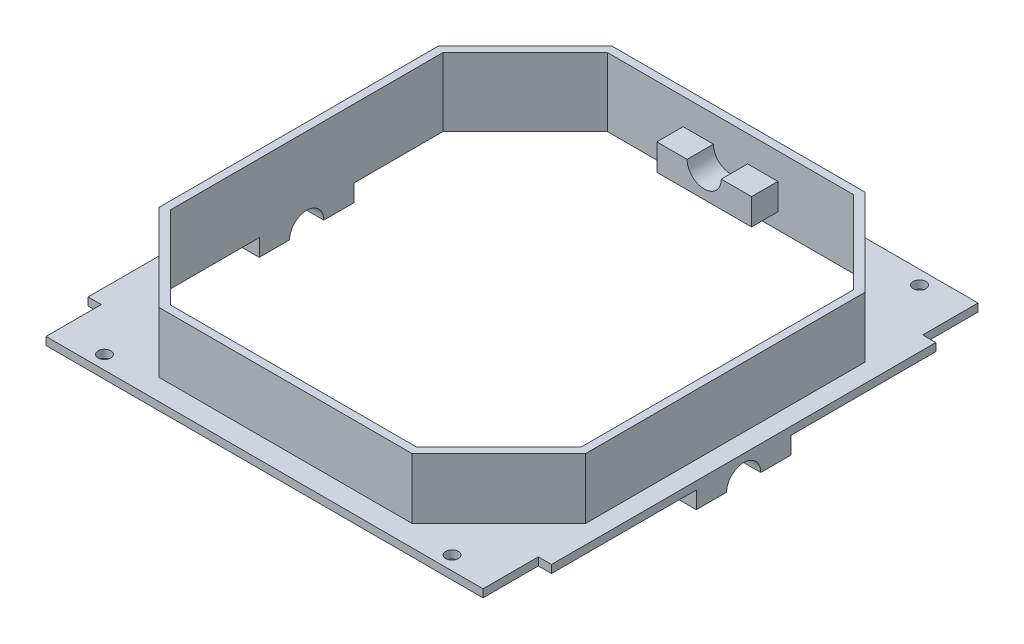
SolidWorks part; units mm, degrees
ref_plane "Front Plane" through (0, 0, 0) normal (0, 0, 1) x (1, 0, 0)
ref_plane "Top Plane" through (0, 0, 0) normal (0, 1, 0) x (1, 0, 0)
ref_plane "Right Plane" through (0, 0, 0) normal (1, 0, 0) x (0, 0, -1)
sketch "Sketch1" plane through (0, 0, 0) normal (0, 1, 0) x (1, 0, 0)
  line L5 (-44, -46.5) -> (44, -46.5)
  line L6 (-44, -46.5) -> (-44, 46.5)
  line L7 (-44, 46.5) -> (44, 46.5)
  line L8 (44, -46.5) -> (44, 46.5)
  line L9 (-44, -46.5) -> (44, 46.5) construction
  line L10 (-44, 46.5) -> (44, -46.5) construction
  point P0 (0, 0)
  dimension "D1" = 88
  dimension "D2" = 93
extrude "Boss-Extrude1" add sketch "Sketch1" along normal blind 13
sketch "Sketch2" plane through (0, 13, 0) normal (0, 1, 0) x (1, 0, 0)
  line L0 (0, 46.5) -> (0, -46.5) construction
  line L1 (-44, -46.5) -> (44, -46.5) construction
  line L2 (-44, 0) -> (44, 0) construction
  line L3 (44, -46.5) -> (44, 46.5) construction
  line L4 (-24, -43) -> (-40.5, -26.5)
  line L5 (-44, 46.5) -> (-44, -46.5) construction
  line L6 (-44, -36.5) -> (-44, -46.5)
  line L7 (-44, -46.5) -> (-34, -46.5)
  line L11 (-24, -43) -> (24, -43)
  line L14 (-34, -46.5) -> (34, -46.5)
  line L15 (-40.5, -26.5) -> (-40.5, 26.5)
  line L17 (-44, -36.5) -> (-44, 36.5)
  line L18 (44, -36.5) -> (44, 36.5)
  line L19 (40.5, -26.5) -> (40.5, 26.5)
  line L20 (44, -46.5) -> (34, -46.5)
  line L21 (44, -36.5) -> (44, -46.5)
  line L22 (24, -43) -> (40.5, -26.5)
  line L23 (24, 43) -> (40.5, 26.5)
  line L24 (44, 36.5) -> (44, 46.5)
  line L25 (44, 46.5) -> (34, 46.5)
  line L26 (-34, 46.5) -> (34, 46.5)
  line L27 (-24, 43) -> (24, 43)
  line L28 (-44, 46.5) -> (-34, 46.5)
  line L29 (-44, 36.5) -> (-44, 46.5)
  line L30 (-24, 43) -> (-40.5, 26.5)
  point P6 (0, 0)
  point P12 (0, 0)
  point P29 (0, -43)
  point P35 (40.5, 0)
  point P37 (-40.5, 0)
  point P40 (0, 43)
  dimension "D1" = 45
  dimension "D2" = 10
  dimension "D3" = 10
  dimension "D4" = 3.5
  dimension "D5" = 3.5
  dimension "D6" = 20
extrude "Cut-Extrude1" cut sketch "Sketch2" against normal offset from surface (11.5 mm away) 1.5 up to face at (0, 0, 0)
sketch "Sketch3" plane through (0, 13, 0) normal (0, 1, 0) x (1, 0, 0)
  line L16 (-23.3787, -41.5) -> (23.3787, -41.5)
  line L17 (23.3787, -41.5) -> (39, -25.8787)
  line L18 (39, -25.8787) -> (39, 25.8787)
  line L19 (39, 25.8787) -> (23.3787, 41.5)
  line L20 (23.3787, 41.5) -> (-23.3787, 41.5)
  line L21 (-23.3787, 41.5) -> (-39, 25.8787)
  line L22 (-39, 25.8787) -> (-39, -25.8787)
  line L23 (-39, -25.8787) -> (-23.3787, -41.5)
  line L24 (-23.3787, -41.5) -> (23.3787, -41.5)
  line L25 (23.3787, -41.5) -> (39, -25.8787)
  line L26 (39, -25.8787) -> (39, 25.8787)
  line L27 (39, 25.8787) -> (23.3787, 41.5)
  line L28 (23.3787, 41.5) -> (-23.3787, 41.5)
  line L29 (-23.3787, 41.5) -> (-39, 25.8787)
  line L30 (-39, 25.8787) -> (-39, -25.8787)
  line L31 (-39, -25.8787) -> (-23.3787, -41.5)
  dimension "D1" = 1.5
extrude "Cut-Extrude2" cut sketch "Sketch3" against normal through all
sketch "Sketch4" plane through (0, 0, -41.5) normal (0, 0, 1) x (1, 0, 0)
  line L0 (0, 0) -> (0, 8) construction
  line L1 (23.3787, 0) -> (-23.3787, 0) construction
  line L2 (3.25, 8) -> (9, 8)
  line L5 (3.25, 8) -> (-3.25, 8) construction
  line L8 (-9, 3) -> (9, 3)
  line L9 (9, 3) -> (9, 8)
  line L10 (23.3787, 13) -> (-23.3787, 13) construction
  line L11 (-9, 3) -> (-9, 8)
  line L12 (-3.25, 8) -> (-9, 8)
  arc A0 (-3.25, 8) -> (3.25, 8) centre (0, 8) ccw
  point P13 (0, 3)
  dimension "D1" = 3.25
  dimension "D2" = 18
  dimension "D3" = 5
  dimension "D4" = 5
extrude "Boss-Extrude2" add sketch "Sketch4" along normal blind 5
sketch "Sketch5" plane through (39, 0, 0) normal (-1, 0, 0) x (0, 0, 1)
  line L0 (0, 0) -> (0, -3.25) construction
  line L2 (25.8787, 0) -> (-25.8787, 0) construction
  line L3 (3.25, -3.25) -> (9, -3.25)
  line L4 (9, -3.25) -> (9, 0)
  line L6 (-9, -3.25) -> (-9, 0)
  line L7 (-3.25, -3.25) -> (-9, -3.25)
  line L8 (-9, 0) -> (9, 0)
  arc A1 (3.25, -3.25) -> (-3.25, -3.25) centre (0, -3.25) ccw
  line M14 (-25.8787, 0) -> (25.8787, 0)
  dimension "D2" = 3.25
  dimension "D1" = 6.5
  dimension "D3" = 18
extrude "Boss-Extrude5" add sketch "Sketch4<2>" against normal blind 5 from surface starting at face at (0, 6.5, 41.5)
sketch "Sketch4<2>" plane through (0, 0, -41.5) normal (0, 0, 1) x (1, 0, 0) same geometry as "Sketch4"
sketch "Sketch6" plane through (0, 1.5, 0) normal (0, 1, 0) x (1, 0, 0)
  line L0 (-44, 0) -> (44, 0) construction
  line L1 (44, -46.5) -> (41.5, -46.5)
  line L2 (44, -46.5) -> (44, -36.5)
  line L3 (44, -36.5) -> (41.5, -36.5)
  line L4 (41.5, -46.5) -> (41.5, -36.5)
  line L5 (44, -46.5) -> (44, 46.5) construction
  line L6 (0, -46.5) -> (0, 46.5) construction
  line L7 (44, 46.5) -> (-44, 46.5) construction
  line L8 (41.5, 46.5) -> (41.5, 36.5)
  line L9 (44, 36.5) -> (41.5, 36.5)
  line L10 (44, 46.5) -> (44, 36.5)
  line L11 (44, 46.5) -> (41.5, 46.5)
  line L12 (-44, 46.5) -> (-41.5, 46.5)
  line L13 (-44, 46.5) -> (-44, 36.5)
  line L14 (-44, 36.5) -> (-41.5, 36.5)
  line L15 (-41.5, 46.5) -> (-41.5, 36.5)
  line L16 (-41.5, -46.5) -> (-41.5, -36.5)
  line L17 (-44, -36.5) -> (-41.5, -36.5)
  line L18 (-44, -46.5) -> (-44, -36.5)
  line L19 (-44, -46.5) -> (-41.5, -46.5)
  point P12 (0, 0)
  point P17 (0, 0)
  dimension "D1" = 2.5
  dimension "D2" = 10
extrude "Cut-Extrude3" cut sketch "Sketch6" against normal through all
sketch "Sketch8" plane through (0, 0, -46.5) normal (0, 0, -1) x (-1, 0, 0)
  line L4 (-41.5, 0) -> (41.5, 0)
  line L5 (41.5, 0) -> (41.5, 1.5)
  line L6 (41.5, 1.5) -> (-41.5, 1.5)
  line L7 (-41.5, 1.5) -> (-41.5, 0)
  line L8 (-41.5, 0) -> (41.5, 0)
  line L9 (41.5, 0) -> (41.5, 1.5)
  line L10 (41.5, 1.5) -> (-41.5, 1.5)
  line L11 (-41.5, 1.5) -> (-41.5, 0)
  dimension "D1" = 0
extrude "Boss-Extrude6" add sketch "Sketch8" along normal blind 0.5
mirror "Mirror1" about plane through (0, 0, 0) normal (0, 0, 1) of "Boss-Extrude6"
sketch "Sketch9" plane through (0, 0, 0) normal (0, 1, 0) x (1, 0, 0)
  line L0 (41.5, -36.5) -> (41.5, -47) construction
  line L1 (-41.5, -47) -> (41.5, -47) construction
  line L2 (-44, 0) -> (44, 0) construction
  line L3 (44, -36.5) -> (44, 36.5) construction
  line L4 (0, -47) -> (0, 47) construction
  line L5 (-41.5, 47) -> (41.5, 47) construction
  circle A0 centre (33, -44.4) radius 1.2
  circle A1 centre (33, 44.4) radius 1.2
  circle A2 centre (-33, 44.4) radius 1.2
  circle A3 centre (-33, -44.4) radius 1.2
  point P12 (0, 0)
  point P18 (0, 0)
  dimension "D1" = 8.5
  dimension "D2" = 2.6
  dimension "D3" = 2.4
extrude "Cut-Extrude4" cut sketch "Sketch9" along normal through all
extrude "Boss-Extrude7" add sketch "Sketch5" against normal up to surface (5 mm away) contours A1 L6 L7 M14 | A1 L3 L4 L8 region at (39, -1.5277, 5.7355) region at (39, -1.5277, -5.7355) up to face at (44, 0.75, 0)
extrude "Boss-Extrude8" add sketch "Sketch5<4>" along normal up to surface (83 mm away) from surface contours A1 L6 L7 M14 | A1 L3 L4 L8 region at (39, -1.5277, 5.7355) region at (39, -1.5277, -5.7355) up to face at (-44, 0.75, 0) starting at face at (-39, 6.5, 0)
sketch "Sketch5<4>" plane through (39, 0, 0) normal (-1, 0, 0) x (0, 0, 1) same geometry as "Sketch5"
